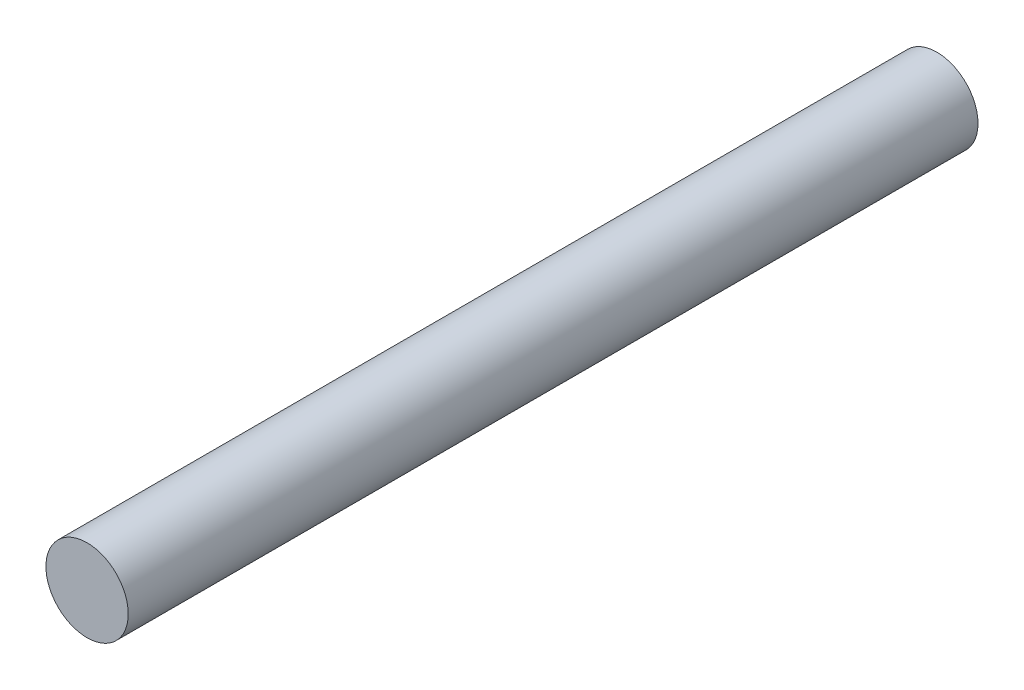
SolidWorks part; units mm, degrees
ref_plane "Front Plane" through (0, 0, 0) normal (0, 0, 1) x (1, 0, 0)
ref_plane "Top Plane" through (0, 0, 0) normal (0, 1, 0) x (1, 0, 0)
ref_plane "Right Plane" through (0, 0, 0) normal (1, 0, 0) x (0, 0, -1)
sketch "Sketch2" plane through (0, 0, 0) normal (0, 0, 1) x (1, 0, 0)
  circle A0 centre (0, 0) radius 3.875
  dimension "D1" = 7.75
extrude "Boss-Extrude1" add sketch "Sketch2" along normal blind 80
